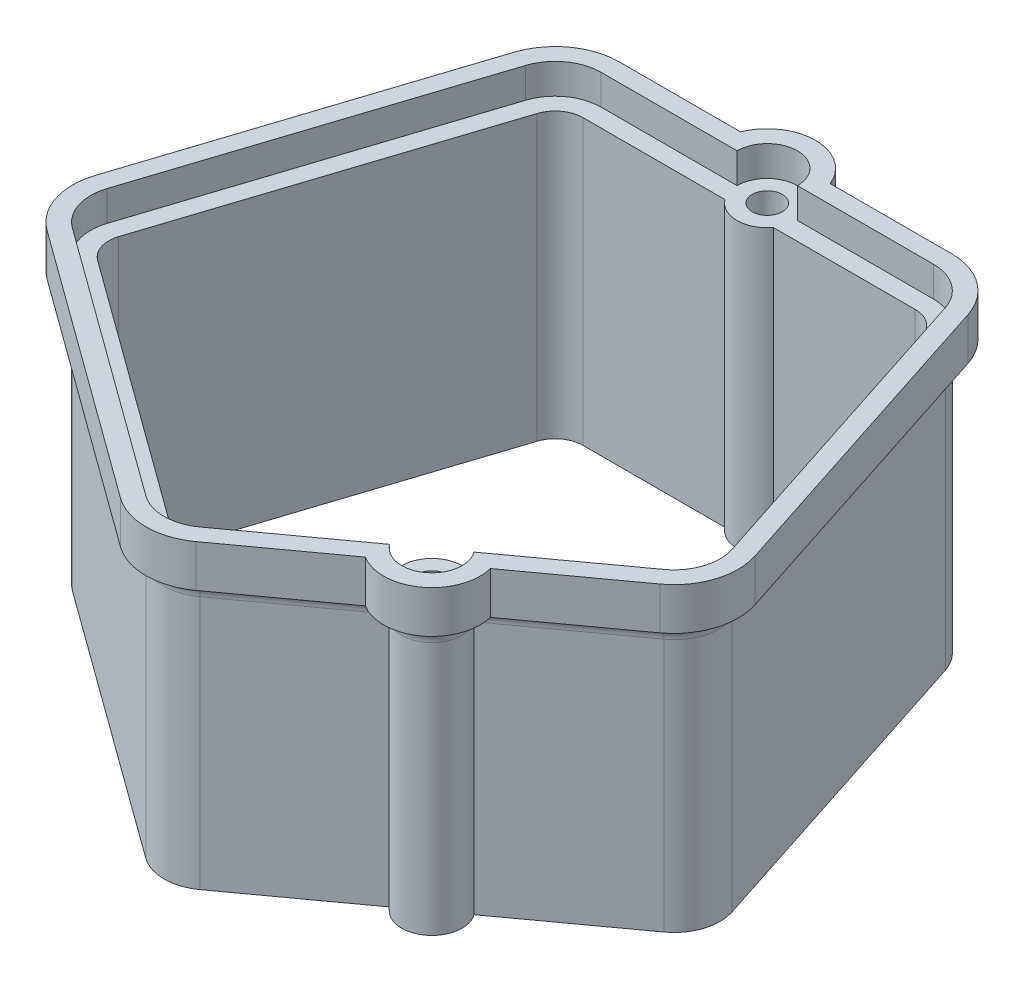
SolidWorks part; units mm, degrees
material "ABS"
ref_plane "Front Plane" through (0, 0, 0) normal (0, 0, 1) x (1, 0, 0)
ref_plane "Top Plane" through (0, 0, 0) normal (0, 1, 0) x (1, 0, 0)
ref_plane "Right Plane" through (0, 0, 0) normal (1, 0, 0) x (0, 0, -1)
sketch "Sketch1" plane through (0, 0, 0) normal (0, 1, 0) x (1, 0, 0)
  line L0 (-42.9604, -16.814) -> (1.5332, -49.1405)
  line L1 (6.9643, -49.1405) -> (25.975, -35.3284)
  line L2 (4.2488, 51.849) -> (4.2488, 50.849)
  line L3 (0.2488, 46.849) -> (-23.2498, 46.849)
  line L4 (-30.4968, 41.5837) -> (-47.4919, -10.7216)
  line L5 (-44.7237, -19.241) -> (-0.2302, -51.5675)
  line L6 (8.7277, -51.5675) -> (27.7384, -37.7554)
  line L7 (33.3256, -38.6403) -> (33.9134, -39.4494)
  line L8 (35.0196, -32.4654) -> (53.2213, -19.241)
  line L9 (55.9894, -10.7216) -> (38.9943, 41.5837)
  line L10 (31.7473, 46.849) -> (9.2488, 46.849)
  line L11 (32.4472, -30.6261) -> (51.4579, -16.814)
  line L12 (53.1362, -11.6487) -> (36.1412, 40.6567)
  line L13 (31.7473, 43.849) -> (8.2488, 43.849)
  line L14 (-23.2498, 43.849) -> (0.2488, 43.849)
  line L15 (-44.6387, -11.6487) -> (-27.6437, 40.6567)
  line L16 (-47.4919, -15.431) -> (47.4919, 15.431) construction
  line L17 (-44.6387, -14.504) -> (44.6387, 14.504) construction
  arc A0 (9.2488, 46.849) -> (4.2488, 51.849) centre (4.2488, 46.849) ccw
  arc A1 (4.2488, 50.849) -> (0.2488, 46.849) centre (4.2488, 46.849) ccw
  arc A2 (-23.2498, 46.849) -> (-30.4968, 41.5837) centre (-23.2498, 39.229) ccw
  arc A3 (-47.4919, -10.7216) -> (-44.7237, -19.241) centre (-40.2448, -13.0763) ccw
  arc A4 (-0.2302, -51.5675) -> (8.7277, -51.5675) centre (4.2488, -45.4028) ccw
  arc A5 (27.7384, -37.7554) -> (33.3256, -38.6403) centre (30.9745, -35.4043) ccw
  arc A6 (33.9134, -39.4494) -> (35.0196, -32.4654) centre (30.9745, -35.4043) ccw
  arc A7 (53.2213, -19.241) -> (55.9894, -10.7216) centre (48.7423, -13.0763) ccw
  arc A8 (38.9943, 41.5837) -> (31.7473, 46.849) centre (31.7473, 39.229) ccw
  arc A9 (-44.6387, -11.6487) -> (-42.9604, -16.814) centre (-40.2448, -13.0763) ccw
  arc A10 (1.5332, -49.1405) -> (6.9643, -49.1405) centre (4.2488, -45.4028) ccw
  circle A11 centre (30.9745, -35.4043) radius 2.5
  arc A12 (32.4472, -30.6261) -> (25.975, -35.3284) centre (30.9745, -35.4043) ccw
  arc A13 (51.4579, -16.814) -> (53.1362, -11.6487) centre (48.7423, -13.0763) ccw
  arc A14 (36.1412, 40.6567) -> (31.7473, 43.849) centre (31.7473, 39.229) ccw
  arc A15 (0.2488, 43.849) -> (8.2488, 43.849) centre (4.2488, 46.849) ccw
  circle A16 centre (4.2488, 46.849) radius 2.5
  arc A17 (-23.2498, 43.849) -> (-27.6437, 40.6567) centre (-23.2498, 39.229) ccw
  arc A36 (4.2488, 51.849) -> (-0.7512, 46.849) centre (4.2488, 46.849) ccw
  arc A37 (33.9134, -39.4494) -> (26.9294, -38.3432) centre (30.9745, -35.4043) cw
  point P58 (0, 0)
  point P60 (0, 0)
extrude "Boss-Extrude1" add sketch "Sketch1" along normal blind 40 contours L9 A8 L10 A0 L2 A1 L3 A2 L4 A3 L5 A4 L6 A5 L7 A6 L8 A7 A17 L14 A15 L13 A14 L12 A13 L11 A12 L1 A10 L0 A9 L15 A16 A11 | A37 L7 A5 L6 | L2 A36 L3 A1 region at (6.7388, 0, -49.339) region at (1.3722, 0, -49.7256) region at (30.3381, 0, 39.4223)
sketch "Sketch2" plane through (0, 40, 0) normal (0, 1, 0) x (1, 0, 0)
  line L1 (-30.4968, 41.5837) -> (-33.35, 42.5108)
  line L2 (-47.4919, -10.7216) -> (-50.345, -9.7946)
  line L3 (-33.35, 42.5108) -> (-50.345, -9.7946)
  line L5 (-23.2498, 46.849) -> (-23.2498, 49.849)
  line L8 (55.9894, -10.7216) -> (38.9943, 41.5837)
  line L9 (31.7473, 46.849) -> (9.2488, 46.849)
  line L10 (-0.7512, 46.849) -> (-23.2498, 46.849)
  line L13 (-30.4968, 41.5837) -> (-47.4919, -10.7216)
  line L21 (-44.7237, -19.241) -> (-0.2302, -51.5675)
  line L22 (8.7277, -51.5675) -> (26.9294, -38.3432)
  line L23 (35.0196, -32.4654) -> (53.2213, -19.241)
  line L24 (55.9894, -10.7216) -> (38.9943, 41.5837)
  line L25 (31.7473, 46.849) -> (9.2488, 46.849)
  line L26 (-0.7512, 46.849) -> (-23.2498, 46.849)
  line L27 (-30.4968, 41.5837) -> (-47.4919, -10.7216)
  line L28 (-44.7237, -19.241) -> (-0.2302, -51.5675)
  line L29 (8.7277, -51.5675) -> (26.9294, -38.3432)
  line L30 (35.0196, -32.4654) -> (53.2213, -19.241)
  line L31 (-23.2498, 49.849) -> (-3.1674, 49.849)
  line L33 (54.9846, -21.6681) -> (38.7377, -33.4722)
  line L34 (10.491, -53.9946) -> (26.738, -42.1905)
  line L35 (-1.9935, -53.9946) -> (-46.4871, -21.6681)
  line L36 (31.7473, 49.849) -> (11.665, 49.849)
  line L37 (41.8475, 42.5108) -> (58.8425, -9.7946)
  arc A0 (-3.1674, 49.849) -> (11.665, 49.849) centre (4.2488, 46.849) cw
  arc A1 (-33.35, 42.5108) -> (-23.2498, 49.849) centre (-23.2498, 39.229) cw
  arc A3 (-50.345, -9.7946) -> (-46.4871, -21.6681) centre (-40.2448, -13.0763) ccw
  arc A5 (41.8475, 42.5108) -> (31.7473, 49.849) centre (31.7473, 39.229) ccw
  arc A6 (58.8425, -9.7946) -> (54.9846, -21.6681) centre (48.7423, -13.0763) cw
  arc A21 (26.738, -42.1905) -> (38.7377, -33.4722) centre (30.9745, -35.4043) ccw
  arc A22 (-1.9935, -53.9946) -> (10.491, -53.9946) centre (4.2488, -45.4028) ccw
  arc A23 (38.9943, 41.5837) -> (31.7473, 46.849) centre (31.7473, 39.229) ccw
  arc A24 (9.2488, 46.849) -> (-0.7512, 46.849) centre (4.2488, 46.849) ccw
  arc A25 (-23.2498, 46.849) -> (-30.4968, 41.5837) centre (-23.2498, 39.229) ccw
  arc A26 (-47.4919, -10.7216) -> (-44.7237, -19.241) centre (-40.2448, -13.0763) ccw
  arc A27 (-0.2302, -51.5675) -> (8.7277, -51.5675) centre (4.2488, -45.4028) ccw
  arc A28 (26.9294, -38.3432) -> (35.0196, -32.4654) centre (30.9745, -35.4043) ccw
  arc A29 (53.2213, -19.241) -> (55.9894, -10.7216) centre (48.7423, -13.0763) ccw
  arc A30 (38.9943, 41.5837) -> (31.7473, 46.849) centre (31.7473, 39.229) ccw
  arc A31 (9.2488, 46.849) -> (-0.7512, 46.849) centre (4.2488, 46.849) ccw
  arc A32 (-23.2498, 46.849) -> (-30.4968, 41.5837) centre (-23.2498, 39.229) ccw
  arc A33 (-47.4919, -10.7216) -> (-44.7237, -19.241) centre (-40.2448, -13.0763) ccw
  arc A34 (-0.2302, -51.5675) -> (8.7277, -51.5675) centre (4.2488, -45.4028) ccw
  arc A35 (26.9294, -38.3432) -> (35.0196, -32.4654) centre (30.9745, -35.4043) ccw
  arc A36 (53.2213, -19.241) -> (55.9894, -10.7216) centre (48.7423, -13.0763) ccw
  line M62 (55.9894, -10.7216) -> (38.9943, 41.5837)
  arc M63 (38.9943, 41.5837) -> (31.7473, 46.849) centre (31.7473, 39.229) ccw
  line M64 (31.7473, 46.849) -> (9.2488, 46.849)
  arc M65 (9.2488, 46.849) -> (-0.7512, 46.849) centre (4.2488, 46.849) ccw
  line M66 (-0.7512, 46.849) -> (-23.2498, 46.849)
  arc M67 (-23.2498, 46.849) -> (-30.4968, 41.5837) centre (-23.2498, 39.229) ccw
  line M68 (-30.4968, 41.5837) -> (-47.4919, -10.7216)
  arc M69 (-47.4919, -10.7216) -> (-44.7237, -19.241) centre (-40.2448, -13.0763) ccw
  line M70 (-44.7237, -19.241) -> (-0.2302, -51.5675)
  arc M71 (-0.2302, -51.5675) -> (8.7277, -51.5675) centre (4.2488, -45.4028) ccw
  line M72 (8.7277, -51.5675) -> (26.9294, -38.3432)
  arc M73 (26.9294, -38.3432) -> (35.0196, -32.4654) centre (30.9745, -35.4043) ccw
  line M74 (35.0196, -32.4654) -> (53.2213, -19.241)
  arc M75 (53.2213, -19.241) -> (55.9894, -10.7216) centre (48.7423, -13.0763) ccw
  dimension "D5" = 3
  dimension "D2" = 3
  dimension "D3" = 3
  dimension "D1" = 0
extrude "Boss-Extrude2" add sketch "Sketch2" along normal blind 5 and the other way blind 2 contours L1 L3 L2 M68 | L35 A22 L34 A21 L33 A6 L37 A5 L36 A0 L31 L5 L2 A3 M66 M65 M64 M63 M62 M75 M74 M73 M72 M71 M70 M69 | A1 L1 L5 M67 region at (-40.4209, 40, -15.8946) region at (-28.3098, 40, -46.1935) region at (-48.9788, 40, 15.9142)
fillet "Fillet1" radius 3 14 edges at (20.498, 38, -46.849) (36.2262, 38, -45.3937) (47.4919, 38, -15.431) (55.9894, 38, 15.431) (-12.0005, 38, -46.849) (-27.7287, 38, -45.3937) (-38.9943, 38, -15.431) (-47.4919, 38, 15.431) (17.8285, 38, 44.9554) (4.2488, 38, 53.0228) (4.2488, 38, -51.849) (33.9134, 38, 39.4494) (44.1204, 38, 25.8532) (-22.477, 38, 35.4043)
sketch "Sketch3" plane through (0, 0, 0) normal (0, -1, 0) x (1, 0, 0)
  line L7 (-44.6387, 11.6487) -> (-27.6437, -40.6567)
  line L8 (1.5332, 49.1405) -> (-42.9604, 16.814)
  line L9 (25.975, 35.3284) -> (6.9643, 49.1405)
  line L10 (51.4579, 16.814) -> (32.4472, 30.6261)
  line L11 (36.1412, -40.6567) -> (53.1362, 11.6487)
  line L12 (8.2488, -43.849) -> (31.7473, -43.849)
  line L13 (-23.2498, -43.849) -> (0.2488, -43.849)
  line L14 (-44.6387, 11.6487) -> (-27.6437, -40.6567)
  line L15 (1.5332, 49.1405) -> (-42.9604, 16.814)
  line L16 (25.975, 35.3284) -> (6.9643, 49.1405)
  line L17 (51.4579, 16.814) -> (32.4472, 30.6261)
  line L18 (36.1412, -40.6567) -> (53.1362, 11.6487)
  line L19 (8.2488, -43.849) -> (31.7473, -43.849)
  line L20 (-23.2498, -43.849) -> (0.2488, -43.849)
  line L21 (38.9943, -41.5837) -> (55.9894, 10.7216)
  line L22 (53.2213, 19.241) -> (35.0196, 32.4654)
  line L23 (26.9294, 38.3432) -> (8.7277, 51.5675)
  line L24 (-0.2302, 51.5675) -> (-44.7237, 19.241)
  line L25 (-47.4919, 10.7216) -> (-30.4968, -41.5837)
  line L26 (-23.2498, -46.849) -> (-0.7512, -46.849)
  line L27 (9.2488, -46.849) -> (31.7473, -46.849)
  line L28 (38.9943, -41.5837) -> (55.9894, 10.7216)
  line L29 (53.2213, 19.241) -> (35.0196, 32.4654)
  line L30 (26.9294, 38.3432) -> (8.7277, 51.5675)
  line L31 (-0.2302, 51.5675) -> (-44.7237, 19.241)
  line L32 (-47.4919, 10.7216) -> (-30.4968, -41.5837)
  line L33 (-23.2498, -46.849) -> (-0.7512, -46.849)
  line L34 (9.2488, -46.849) -> (31.7473, -46.849)
  circle A1 centre (30.9745, 35.4043) radius 2.5
  circle A2 centre (30.9745, 35.4043) radius 2.5
  circle A3 centre (4.2488, -46.849) radius 2.5
  circle A4 centre (4.2488, -46.849) radius 2.5
  arc A7 (-27.6437, -40.6567) -> (-23.2498, -43.849) centre (-23.2498, -39.229) ccw
  arc A8 (-42.9604, 16.814) -> (-44.6387, 11.6487) centre (-40.2448, 13.0763) ccw
  arc A9 (6.9643, 49.1405) -> (1.5332, 49.1405) centre (4.2488, 45.4028) ccw
  arc A10 (25.975, 35.3284) -> (32.4472, 30.6261) centre (30.9745, 35.4043) ccw
  arc A11 (53.1362, 11.6487) -> (51.4579, 16.814) centre (48.7423, 13.0763) ccw
  arc A12 (31.7473, -43.849) -> (36.1412, -40.6567) centre (31.7473, -39.229) ccw
  arc A13 (8.2488, -43.849) -> (0.2488, -43.849) centre (4.2488, -46.849) ccw
  arc A14 (-27.6437, -40.6567) -> (-23.2498, -43.849) centre (-23.2498, -39.229) ccw
  arc A15 (-42.9604, 16.814) -> (-44.6387, 11.6487) centre (-40.2448, 13.0763) ccw
  arc A16 (6.9643, 49.1405) -> (1.5332, 49.1405) centre (4.2488, 45.4028) ccw
  arc A17 (25.975, 35.3284) -> (32.4472, 30.6261) centre (30.9745, 35.4043) ccw
  arc A18 (53.1362, 11.6487) -> (51.4579, 16.814) centre (48.7423, 13.0763) ccw
  arc A19 (31.7473, -43.849) -> (36.1412, -40.6567) centre (31.7473, -39.229) ccw
  arc A20 (8.2488, -43.849) -> (0.2488, -43.849) centre (4.2488, -46.849) ccw
  arc A25 (55.9894, 10.7216) -> (53.2213, 19.241) centre (48.7423, 13.0763) ccw
  arc A26 (35.0196, 32.4654) -> (26.9294, 38.3432) centre (30.9745, 35.4043) ccw
  arc A27 (8.7277, 51.5675) -> (-0.2302, 51.5675) centre (4.2488, 45.4028) ccw
  arc A28 (-44.7237, 19.241) -> (-47.4919, 10.7216) centre (-40.2448, 13.0763) ccw
  arc A29 (-30.4968, -41.5837) -> (-23.2498, -46.849) centre (-23.2498, -39.229) ccw
  arc A30 (-0.7512, -46.849) -> (9.2488, -46.849) centre (4.2488, -46.849) ccw
  arc A31 (31.7473, -46.849) -> (38.9943, -41.5837) centre (31.7473, -39.229) ccw
  arc A32 (55.9894, 10.7216) -> (53.2213, 19.241) centre (48.7423, 13.0763) ccw
  arc A33 (35.0196, 32.4654) -> (26.9294, 38.3432) centre (30.9745, 35.4043) ccw
  arc A34 (8.7277, 51.5675) -> (-0.2302, 51.5675) centre (4.2488, 45.4028) ccw
  arc A35 (-44.7237, 19.241) -> (-47.4919, 10.7216) centre (-40.2448, 13.0763) ccw
  arc A36 (-30.4968, -41.5837) -> (-23.2498, -46.849) centre (-23.2498, -39.229) ccw
  arc A37 (-0.7512, -46.849) -> (9.2488, -46.849) centre (4.2488, -46.849) ccw
  arc A38 (31.7473, -46.849) -> (38.9943, -41.5837) centre (31.7473, -39.229) ccw
  dimension "D1" = 0
  dimension "D2" = 0
  dimension "D3" = 0
  dimension "D4" = 0
extrude "Boss-Extrude3" add sketch "Sketch3" along normal blind 7
